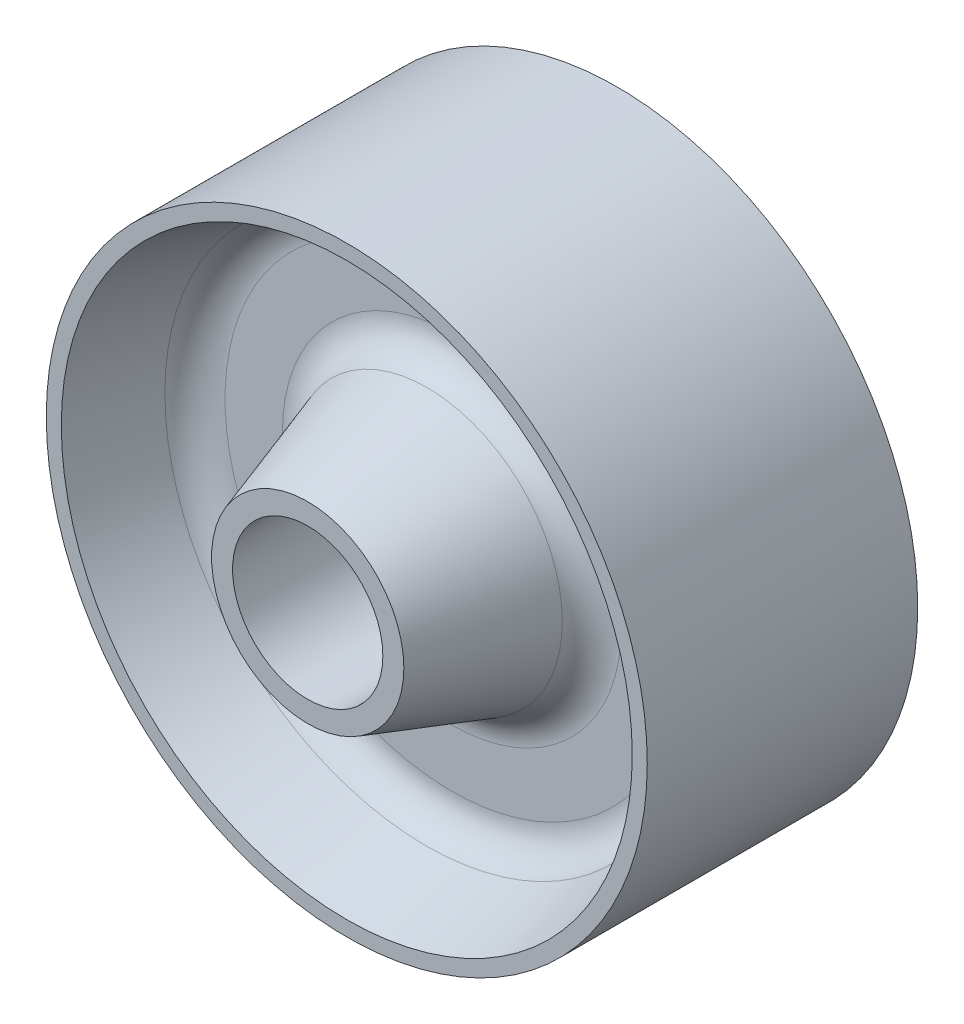
SolidWorks part; units mm, degrees
material "Gray Cast Iron"
ref_plane "Front Plane" through (0, 0, 0) normal (0, 0, 1) x (1, 0, 0)
ref_plane "Top Plane" through (0, 0, 0) normal (0, 1, 0) x (1, 0, 0)
ref_plane "Right Plane" through (0, 0, 0) normal (1, 0, 0) x (0, 0, -1)
sketch "Sketch1" plane through (0, 0, 0) normal (1, 0, 0) x (0, 0, -1)
  line L0 (0, 42.8674) -> (0, -20.3907) construction
  line L1 (-41.4444, 0) -> (35.5536, 0) construction
  line L2 (-22.5, 50) -> (22.5, 50)
  line L3 (22.5, 50) -> (22.5, 47.5)
  line L4 (22.5, 47.5) -> (9.2643, 43.5)
  line L5 (5, 37.7566) -> (5, 28.2025)
  line L6 (9.1342, 22.5) -> (29, 16)
  line L8 (29, 16) -> (29, 12.5)
  line L9 (29, 12.5) -> (-29, 12.5)
  line L10 (-29, 12.5) -> (-29, 16)
  line L12 (-29, 16) -> (-9.1342, 22.5)
  line L13 (-5, 28.2025) -> (-5, 37.7566)
  line L14 (-9.2643, 43.5) -> (-22.5, 47.5)
  line L15 (-22.5, 47.5) -> (-22.5, 50)
  arc A0 (5, 37.7566) -> (9.2643, 43.5) centre (11, 37.7566) cw
  arc A1 (-5, 37.7566) -> (-9.2643, 43.5) centre (-11, 37.7566) ccw
  arc A2 (9.1342, 22.5) -> (5, 28.2025) centre (11, 28.2025) cw
  arc A3 (-5, 28.2025) -> (-9.1342, 22.5) centre (-11, 28.2025) cw
  dimension "D4" = 6
  dimension "D5" = 6
  dimension "D1" = 22.5
  dimension "D2" = 22.5
  dimension "D3" = 29
  dimension "D6" = 29
  dimension "D7" = 5
  dimension "D8" = 5
  dimension "D9" = 43.5
  dimension "D10" = 43.5
  dimension "D11" = 22.5
  dimension "D12" = 22.5
  dimension "D13" = 16
  dimension "D14" = 16
  dimension "D15" = 12.5
  dimension "D16" = 47.5
  dimension "D17" = 47.5
  dimension "D18" = 50
revolve "Revolve1" add sketch "Sketch1" angle 360 about L1
